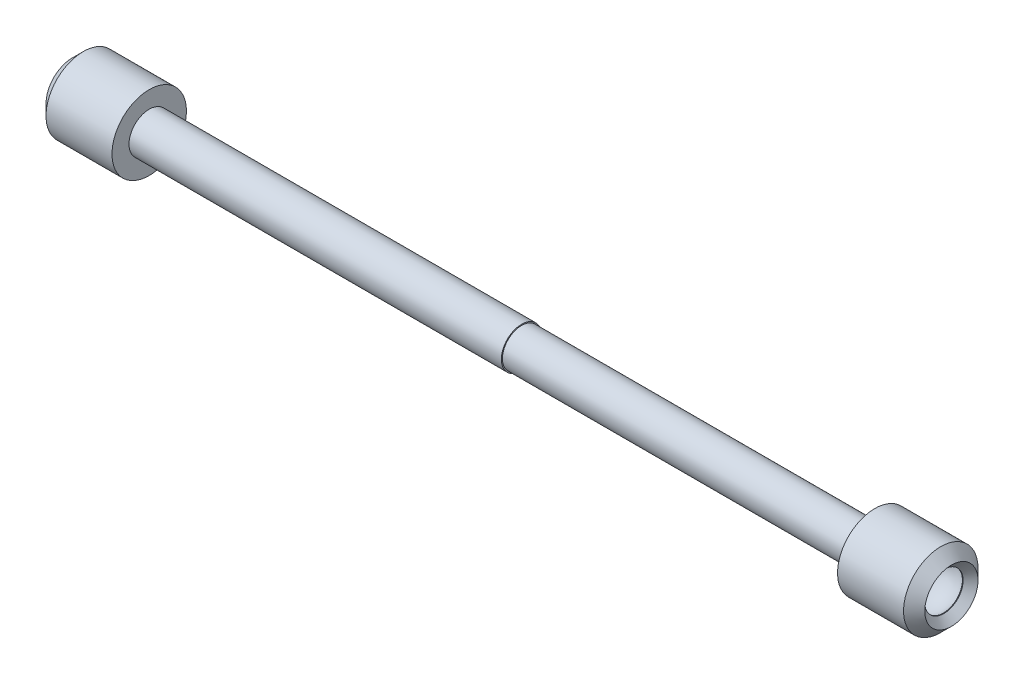
SolidWorks part; units mm, degrees
ref_plane "Płaszczyzna przednia" through (0, 0, 0) normal (0, 0, 1) x (1, 0, 0)
ref_plane "Płaszczyzna górna" through (0, 0, 0) normal (0, 1, 0) x (1, 0, 0)
ref_plane "Płaszczyzna prawa" through (0, 0, 0) normal (1, 0, 0) x (0, 0, -1)
sketch "Szkic1" plane through (0, 0, 0) normal (1, 0, 0) x (0, 0, -1)
  circle A0 centre (0, 0) radius 9
  dimension "D1" = 18
extrude "Dodanie-wyciągnięcie1" add sketch "Szkic1" along normal blind 166
sketch "Szkic2" plane through (0, 0, 0) normal (-1, 0, 0) x (0, 0, 1)
  circle A0 centre (0, 0) radius 9.5
  dimension "D1" = 19
extrude "Dodanie-wyciągnięcie2" add sketch "Szkic2" along normal blind 175
sketch "Szkic3" plane through (166, 0, 0) normal (1, 0, 0) x (0, 0, -1)
  circle A0 centre (0, 0) radius 17.5
  dimension "D1" = 35
extrude "Dodanie-wyciągnięcie3" add sketch "Szkic3" along normal blind 36
chamfer "Sfazowanie1" distance 5 angle 45 1 edges at (202, 0, -17.5)
sketch "Szkic8" plane through (202, 0, 0) normal (1, 0, 0) x (0, 0, -1)
  circle A0 centre (0, 0) radius 9
  dimension "D1" = 18
extrude "Wytnij-wyciągnięcie1" cut sketch "Szkic8" against normal blind 10
sketch "Szkic4" plane through (0, 0, 0) normal (0, 0, 1) x (1, 0, 0)
  line L0 (202, -12.5) -> (202, 12.5) construction
  line L1 (189.5, 12.5) -> (189.5, -12.5)
  line L3 (55, 0) -> (-55, 0) construction
  arc A0 (189.5, -12.5) -> (189.5, 12.5) centre (189.5, 0) ccw
  point P1 (0, 0)
  point P6 (191, 33.3984)
  dimension "D1" = 25
revolve "Wycięcie-obrót9" cut sketch "Szkic4" angle 360 about L1
chamfer "Sfazowanie3" distance 3.5 angle 45 1 edges at (202, 0, -9)
sketch "Szkic9" plane through (0, 0, 0) normal (0, 0, 1) x (1, 0, 0)
  line L0 (-175, 0) -> (166, 0) construction
  line L1 (-175, 9.5) -> (-175, -9.5) construction
  line L2 (166, 17.5) -> (166, -17.5) construction
sketch "Szkic11" plane through (0, 0, 0) normal (0, 0, 1) x (1, 0, 0)
  line L0 (-4.5, 58.5822) -> (-4.5, -58.5822) construction
  line L2 (-175, 0) -> (166, 0) construction
  point P2 (-4.5, 0)
  point P5 (-4.5, 0)
ref_plane "Płaszczyzna Lustra" through (-4.5, 0, 0) normal (-1, 0, 0) x (0, 0, 1)
mirror "Lustro7" about plane through (-4.5, 0, 0) normal (-1, 0, 0) of "Sfazowanie3", "Wycięcie-obrót9", "Wytnij-wyciągnięcie1", "Sfazowanie1", "Dodanie-wyciągnięcie3"
